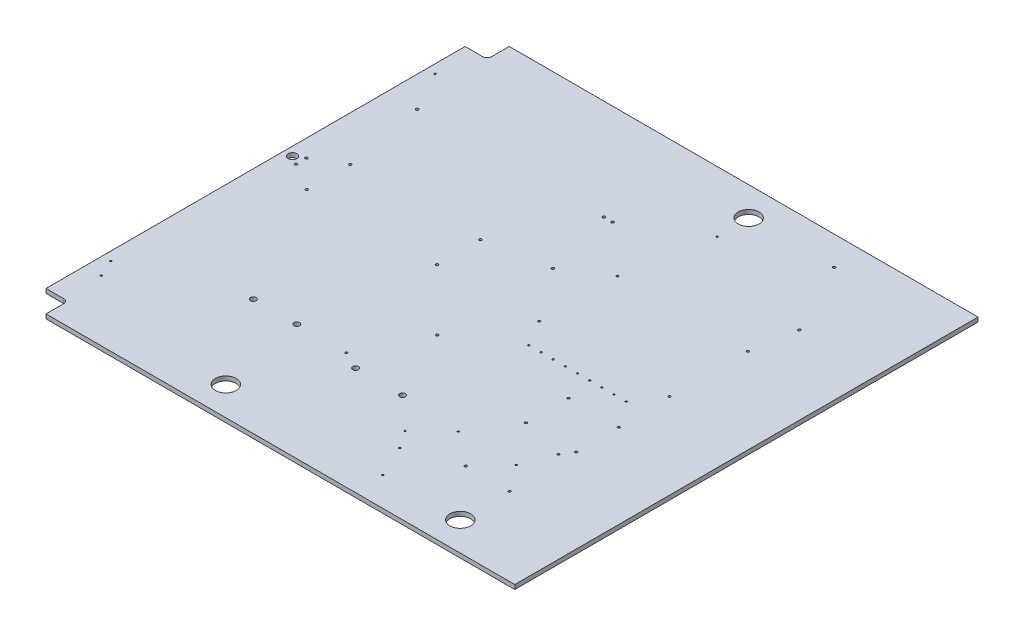
SolidWorks part; units mm, degrees
ref_plane "Front Plane" through (0, 0, 0) normal (0, 0, 1) x (1, 0, 0)
ref_plane "Top Plane" through (0, 0, 0) normal (0, 1, 0) x (1, 0, 0)
ref_plane "Right Plane" through (0, 0, 0) normal (1, 0, 0) x (0, 0, -1)
sketch "Sketch1" plane through (0, 0, 0) normal (1, 0, 0) x (0, 0, -1)
  line L0 (0, 0) -> (-533.4, 0)
  line L1 (-533.4, 0) -> (-533.4, 5)
  line L2 (-533.4, 5) -> (0, 5)
  line L6 (0, 5) -> (0, 0)
  dimension "D1" = 533.4
extrude "Boss-Extrude1" add sketch "Sketch1" along normal blind 565.15
sketch "BotthomHoles-Sketch2" plane through (0, 5, 0) normal (0, 1, 0) x (1, 0, 0)
  line L1 (565.15, 0) -> (565.15, -533.4) construction
  line L2 (565.15, -533.4) -> (0, -533.4) construction
  line L3 (565.15, 0) -> (0, 0) construction
  line L4 (0, 0) -> (0, -533.4) construction
  circle A0 centre (334.275, -33.175) radius 12
  circle A25 centre (199.275, -500.225) radius 12
  circle A26 centre (469.275, -500.225) radius 12
  dimension "D10" = 24
  dimension "D2" = 95.875
  dimension "D3" = 270
  dimension "D4" = 135
  dimension "D5" = 33.175
  dimension "D6" = 33.175
  dimension "D8" = 500.225
  dimension "D7" = 199.275
  dimension "D9" = 334.275
  dimension "D11" = 469.275
extrude "BottomStepperHoles-Cut-Extrude1" cut sketch "BotthomHoles-Sketch2" against normal through all
sketch "BottomPSUHolesSketch2" plane through (0, 5, 0) normal (0, 1, 0) x (1, 0, 0)
  line L0 (0, 0) -> (0, -533.4) construction
  line L1 (565.15, -533.4) -> (0, -533.4) construction
  line L2 (565.15, 0) -> (0, 0) construction
  circle A0 centre (201.5, -209.2) radius 1.5
  circle A1 centre (201.5, -259.2) radius 1.5
  circle A2 centre (51.5, -209.2) radius 1.5
  circle A3 centre (51.5, -259.2) radius 1.5
  circle A6 centre (180, -399.2) radius 3.25
  circle A7 centre (130, -399.2) radius 3.25
  circle A8 centre (257.75, -409.2) radius 3.25
  circle A9 centre (311.75, -409.2) radius 3.25
  dimension "D4" = 6.5
  dimension "D3" = 51.5
  dimension "D1" = 150
  dimension "D2" = 50
  dimension "D7" = 209.2
  dimension "D5" = 50
  dimension "D8" = 140
  dimension "D10" = 134.2
  dimension "D11" = 274.2
  dimension "D12" = 324.2
  dimension "D13" = 201.5
  dimension "D14" = 54
  dimension "D15" = 77.75
  dimension "D16" = 10
  dimension "D9" = 78.5
  dimension "D17" = 130
  dimension "D18" = 124.2
  dimension "D19" = 257.75
  dimension "D20" = 311.75
extrude "BottomPSUHolesCut-Extrude1" cut sketch "BottomPSUHolesSketch2" against normal through all
sketch "OctopusHolesSketch2" plane through (0, 5, 0) normal (0, 1, 0) x (1, 0, 0)
  line L0 (0, 0) -> (0, -533.4) construction
  line L1 (565.15, -533.4) -> (0, -533.4) construction
  circle A0 centre (316.75, -256.7) radius 1.35
  circle A1 centre (466.75, -256.7) radius 1.35
  circle A2 centre (316.75, -166.7) radius 1.35
  circle A3 centre (466.75, -166.7) radius 1.35
  dimension "D1" = 150
  dimension "D3" = 2.7
  dimension "D2" = 90
  dimension "D4" = 115.25
  dimension "D5" = 42.5
  dimension "D6" = 316.75
  dimension "D7" = 466.75
  dimension "D8" = 276.7
  dimension "D9" = 366.7
extrude "OctopusMountHolesCut-Extrude1" cut sketch "OctopusHolesSketch2" against normal through all
sketch "PowrCableGuideMountHolesSketch2" plane through (0, 5, 0) normal (0, 1, 0) x (1, 0, 0)
  line L0 (0, 0) -> (0, -533.4) construction
  line L1 (565.15, -533.4) -> (0, -533.4) construction
  circle A0 centre (271.75, -329.2) radius 1.5
  circle A1 centre (271.75, -196.2) radius 1.5
  dimension "D2" = 3
  dimension "D1" = 133
  dimension "D3" = 45
  dimension "D5" = 271.75
  dimension "D6" = 337.2
  dimension "D7" = 204.2
  dimension "D4" = 29.5
extrude "PowerCableGuideMountHolesCut-Extrude1" cut sketch "PowrCableGuideMountHolesSketch2" against normal through all
sketch "RPIHolesSketch2" plane through (0, 5, 0) normal (0, 1, 0) x (1, 0, 0)
  line L0 (0, 0) -> (0, -533.4) construction
  line L1 (565.15, -533.4) -> (0, -533.4) construction
  circle A4 centre (468.25, -316.7) radius 1.35
  circle A5 centre (468.25, -365.7) radius 1.35
  circle A6 centre (410.25, -316.7) radius 1.35
  circle A7 centre (410.25, -365.7) radius 1.35
  point P4 (282.575, -533.4)
  dimension "D7" = 2.7
  dimension "D1" = 58
  dimension "D2" = 49
  dimension "D3" = 60
  dimension "D4" = 1.5
  dimension "D5" = 410.25
  dimension "D6" = 468.25
  dimension "D8" = 167.7
  dimension "D9" = 216.7
extrude "RPIMountHolesCut-Extrude1" cut sketch "RPIHolesSketch2" against normal through all
sketch "DragChainAndCableGuideHolesSketch2" plane through (0, 5, 0) normal (0, 1, 0) x (1, 0, 0)
  line L3 (565.15, -533.4) -> (0, -533.4) construction
  line L9 (0, 0) -> (0, -533.4) construction
  circle A11 centre (260, -115.65) radius 1.5
  circle A12 centre (10, -234.2) radius 5
  circle A17 centre (475, -115.65) radius 1.5
  circle A18 centre (250, -115.65) radius 1.5
  circle A19 centre (35, -115.65) radius 1.5
  circle A20 centre (20, -240.2) radius 1.5
  circle A21 centre (20, -228.2) radius 1.5
  dimension "D17" = 3
  dimension "D10" = 10
  dimension "D26" = 3
  dimension "D13" = 299.2
  dimension "D15" = 260
  dimension "D5" = 215
  dimension "D16" = 8.25
  dimension "D18" = 475
  dimension "D19" = 215
  dimension "D20" = 10
  dimension "D22" = 35
  dimension "D23" = 250
  dimension "D6" = 25
  dimension "D11" = 10
  dimension "D21" = 6
  dimension "D24" = 6
  dimension "D25" = 20
  dimension "D3" = 417.75
extrude "CragChainAndCableGuideHolesCut-Extrude1" cut sketch "DragChainAndCableGuideHolesSketch2" against normal through all
sketch "Sketch2" plane through (0, 5, 0) normal (0, 1, 0) x (1, 0, 0)
  line L0 (565.15, -533.4) -> (0, -533.4) construction
  line L1 (0, 0) -> (0, -533.4) construction
  circle A0 centre (334.75, -286.7) radius 1
  circle A1 centre (348.75, -286.7) radius 1
  circle A2 centre (362.75, -286.7) radius 1
  circle A3 centre (376.75, -286.7) radius 1
  circle A4 centre (390.75, -286.7) radius 1
  circle A5 centre (404.75, -286.7) radius 1
  circle A6 centre (418.75, -286.7) radius 1
  circle A7 centre (432.75, -286.7) radius 1
  circle A8 centre (446.75, -286.7) radius 1
  dimension "D10" = 14
  dimension "D11" = 2
  dimension "D1" = 18
  dimension "D2" = 14
  dimension "D3" = 14
  dimension "D4" = 14
  dimension "D5" = 14
  dimension "D6" = 14
  dimension "D7" = 14
  dimension "D8" = 14
  dimension "D9" = 30
  dimension "D12" = 246.7
  dimension "D13" = 334.75
extrude "OctopusRouting holesCut-Extrude1" cut sketch "Sketch2" against normal through all
sketch "PiPowerAndSSRControlSketch3" plane through (0, 5, 0) normal (0, 1, 0) x (1, 0, 0)
  line L0 (565.15, -533.4) -> (0, -533.4) construction
  line L1 (0, 0) -> (0, -533.4) construction
  line L2 (565.15, -533.4) -> (0, -533.4) construction
  circle A10 centre (237, -399.2) radius 1.25
  circle A11 centre (460.5, -378.4) radius 1.25
  dimension "D16" = 134.2
  dimension "D18" = 237
  dimension "D19" = 460.5
  dimension "D20" = 155
extrude "PiPowerAndSSRControlCuts-Extrude1" cut sketch "PiPowerAndSSRControlSketch3" against normal through all
sketch "CornerCableKnotchesSketch4" plane through (0, 5, 0) normal (0, 1, 0) x (1, 0, 0)
  line L0 (0, -25.4) -> (20.4, -25.4)
  line L1 (25.4, 0) -> (25.4, -20.4)
  line L2 (565.15, 0) -> (0, 0) construction
  line L3 (0, -25.4) -> (0, 0)
  line L4 (0, 0) -> (0, -533.4) construction
  line L5 (0, 0) -> (25.4, 0)
  line L6 (0, -508) -> (20.4, -508)
  line L7 (25.4, -513) -> (25.4, -533.4)
  line L8 (565.15, -533.4) -> (0, -533.4) construction
  line L9 (0, -508) -> (0, -533.4)
  line L10 (0, -533.4) -> (25.4, -533.4)
  arc A0 (20.4, -25.4) -> (25.4, -20.4) centre (20.4, -20.4) ccw
  arc A1 (25.4, -513) -> (20.4, -508) centre (20.4, -513) ccw
  circle A2 centre (25, -115.65) radius 5 construction
  dimension "D1" = 25.4
extrude "CornerCableKnotchCut-Extrude1" cut sketch "CornerCableKnotchesSketch4" against normal through all
sketch "Z1 pathsSketch4" plane through (0, 5, 0) normal (0, 1, 0) x (1, 0, 0)
  line L2 (0, -25.4) -> (0, -508) construction
  line L3 (565.15, -533.4) -> (25.4, -533.4) construction
  circle A0 centre (432.75, -33.175) radius 1.5
  circle A1 centre (475, -115.65) radius 1.5 construction
  dimension "D1" = 432.75
  dimension "D2" = 500.225
extrude "Z1 patgsCut-Extrude1" cut sketch "Z1 pathsSketch4" against normal through all
sketch "Z2PathsSketch5" plane through (0, 5, 0) normal (0, 1, 0) x (1, 0, 0)
  line L0 (565.15, -533.4) -> (25.4, -533.4) construction
  line L1 (0, -25.4) -> (0, -508) construction
  circle A0 centre (380, -500.225) radius 1
  circle A1 centre (380, -413.4) radius 1
  circle A2 centre (446.75, -413.4) radius 1
  circle A3 centre (446.75, -286.7) radius 1 construction
  dimension "D1" = 33.175
  dimension "D2" = 120
  dimension "D3" = 380
  dimension "D4" = 446.75
extrude "Z2PathsCut-Extrude2" cut sketch "Z2PathsSketch5" against normal through all
sketch "ZPathsSketch4" plane through (0, 5, 0) normal (0, 1, 0) x (1, 0, 0)
  line L0 (565.15, -533.4) -> (25.4, -533.4) construction
  line L1 (0, -25.4) -> (0, -508) construction
  circle A0 centre (469.275, -443.4) radius 1.35
  circle A1 centre (418.75, -443.4) radius 1.35
  circle A2 centre (410.25, -365.7) radius 1.35 construction
  dimension "D1" = 90
  dimension "D2" = 469.275
  dimension "D3" = 418.75
extrude "ZPathsCut-Extrude1" cut sketch "ZPathsSketch4" against normal through all
sketch "LeftGantryAndExtruderPathsSketch4" plane through (0, 5, 0) normal (0, 1, 0) x (1, 0, 0)
  line L0 (565.15, -533.4) -> (25.4, -533.4) construction
  line L1 (0, -25.4) -> (0, -508) construction
  circle A0 centre (348.75, -443.4) radius 1
  circle A1 centre (362.75, -463.4) radius 1
  circle A2 centre (334.75, -286.7) radius 1 construction
  circle A3 centre (10, -443.4) radius 1
  circle A4 centre (19, -463.4) radius 1
  dimension "D1" = 70
  dimension "D2" = 90
  dimension "D3" = 10
  dimension "D4" = 19
  dimension "D5" = 348.75
  dimension "D6" = 362.75
extrude "LeftGantryAndExtruderPathsCut-Extrude1" cut sketch "LeftGantryAndExtruderPathsSketch4" against normal through all
sketch "RightGantryPathsSketch5" plane through (0, 5, 0) normal (0, 1, 0) x (1, 0, 0)
  line L0 (565.15, -533.4) -> (25.4, -533.4) construction
  line L1 (0, -25.4) -> (0, -508) construction
  circle A0 centre (334.75, -70) radius 1
  circle A1 centre (334.75, -286.7) radius 1 construction
  circle A2 centre (10, -70) radius 1
  dimension "D1" = 463.4
  dimension "D2" = 10
  dimension "D3" = 334.75
extrude "RightGantryPathsCut-Extrude2" cut sketch "RightGantryPathsSketch5" against normal through all
equation "\"RailThickness\"= .125in'Spec"
equation "\"Nema17MountStepperHoleDiameter\"= 24mm'Spec"
equation "\"SideRailLength\"= 21.75in"
equation "\"D10@BotthomHoles-Sketch2\" = \"Nema17MountStepperHoleDiameter\""
equation "\"D1@Boss-Extrude1\"=\"LowerEnclosureLength\""
equation "\"BedLength\"= \"BuildPlateLength\""
equation "\"DistanceBetweenFrontToBackStepperHoles\"= \"BedLength\" - \"BuildPlateStandoffHolesDistanceFromFrontOrBackSide\" * 2'Equals 270"
equation "\"LowerEnclosureThickness\"= 5mm"
equation "\"FrontOrBackRailLength\"= 20.5in"
equation "\"D1@Sketch1\"=\"LowerEncloseWidth\""
equation "\"D2@Sketch1\"=\"LowerEnclosureThickness\""
equation "\"24VPSUMountingHolesShortDistanceBetween\"= 50mm'Yours may differ"
equation "\"24VPSUMountingHolesLongDistanceBetween\"= 150mm'Yours may differ"
equation "\"24VPSUMountingHoleOffsetFromEitherSide\"= 32.5mm'Yours may differ"
equation "\"24VPSUMountingHoleDiameter\"= 3mm'Yours may differ"
equation "\"D6@BottomPSUHolesSketch2\" = \"24VPSUMountingHoleDiameter\""
equation "\"RPi4BoardMountingHoleDiameter\"= 2.7mm'Spec"
equation "\"OctopusV1.1BoardMountingHoleOffsetFromAllEdges\"= 5mm'Spec"
equation "\"OctopusV1.1BoardMountingHoleLengthDistanceBetween\"= 150mm'Spec"
equation "\"OctopusV1.1BoardMountingHoleWidthDistanceBetween\"= 90mm'Spec"
equation "\"D7@RPIHolesSketch2\" = \"RPi4BoardMountingHoleDiameter\""
equation "\"RPi4BoardMountingHoleLengthDistanceBetween\"= 58mm'Spec"
equation "\"OctopusV1.1BoardMountingHoleDiameter\"= 2.7mm'Spec"
equation "\"CWD4890MountingHoleWidthDistance\"= 50mm'Spec"
equation "\"24VPSULength\"= 213mm'Spec"
equation "\"D3@OctopusHolesSketch2\"=\"OctopusV1.1BoardMountingHoleDiameter\""
equation "\"24VPSUMountingHoleOffsetFromFront\"= 32.5mm"
equation "\"DistanceBetween24VPSUAndOctopus\"= \"24VPSUMountingHoleOffsetFromFront\" + \"OctopusV1.1BoardMountingHoleOffsetFromAllEdges\" + 77.75'77.75mm gives 10mm before and after 60mm cable guide"
equation "\"GapBetweenVerticalSupportsAndRails\"= \"RailThickness\" * 2"
equation "\"LowerEncloseWidth\"= \"FrontOrBackRailLength\" + \"GapBetweenVerticalSupportsAndRails\" * 2"
equation "\"Nema17MountStepperHoleFromBack\"= 30mm"
equation "\"D2@BotthomHoles-Sketch2\"=\"DistanceFromFrontSideToFirstLeftStepperHoleMountYSValue\" + \"Nema17StepperMountSlotDistance\"/2 + \"GapBetweenVerticalSupportsAndRails\""
equation "\"D3@BotthomHoles-Sketch2\"=\"DistanceBetweenFrontToBackStepperHoles\""
equation "\"D4@BotthomHoles-Sketch2\"=\"DistanceBetweenFrontToBackStepperHoles\"/2"
equation "\"D5@BotthomHoles-Sketch2\"=\"Nema17MountStepperHoleFromBack\" + \"RailThickness\""
equation "\"D6@BotthomHoles-Sketch2\"=\"Nema17MountStepperHoleFromBack\" + \"RailThickness\""
equation "\"LowerEnclosureLength\"= \"SideRailLength\" + \"GapBetweenVerticalSupportsAndRails\" * 2"
equation "\"DistanceFromFrontSideToFirstLeftStepperHoleMountYSValue\"= 74.025mm"
equation "\"BuildPlateStandoffHolesDistanceFromFrontOrBackSide\"= 41mm"
equation "\"BuildPlateLength\"= 352mm'Spec"
equation "\"D1@BottomPSUHolesSketch2\"=\"24VPSUMountingHolesLongDistanceBetween\""
equation "\"D2@BottomPSUHolesSketch2\"=\"24VPSUMountingHolesShortDistanceBetween\""
equation "\"24VPSUOffsetFromBack\"= ( \"24VPSULength\" - \"24VPSUMountingHolesLongDistanceBetween\" ) / 2 + 20mm"
equation "\"24VPSUOffsetFromRightSide\"= ( \"LowerEncloseWidth\" - \"24VPSUWidth\" ) / 2"
equation "\"24VPSUWidth\"= 115mm'Yours may differ"
equation "\"D3@BottomPSUHolesSketch2\"=\"24VPSUOffsetFromBack\""
equation "\"D1@OctopusHolesSketch2\"=\"OctopusV1.1BoardMountingHoleLengthDistanceBetween\""
equation "\"D2@OctopusHolesSketch2\"=\"OctopusV1.1BoardMountingHoleWidthDistanceBetween\""
equation "\"D4@OctopusHolesSketch2\" = \"DistanceBetween24VPSUAndOctopus\""
equation "\"RPI4BoardMountingHoleWidthDistanceBetween\"= 49mm"
equation "\"D7@BottomPSUHolesSketch2\"=\"24VPSUOffsetFromRightSide\""
equation "\"D1@RPIHolesSketch2\"=\"RPi4BoardMountingHoleLengthDistanceBetween\""
equation "\"D2@RPIHolesSketch2\"=\"RPI4BoardMountingHoleWidthDistanceBetween\""
equation "\"D5@BottomPSUHolesSketch2\"=\"CWD4890MountingHoleWidthDistance\""
equation "\"OctopusV1.1ToPSUNegTerminalOffset\"= \"24VPSUNegTerminalOffsetFromSide\" - \"24VPSUMountingHoleOffsetFromEitherSide\" + \"OctopusV1.1NegTerminalOffsetFromSide\" + \"OctopusV1.1BoardMountingHoleOffsetFromAllEdges\""
equation "\"24VPSUNegTerminalOffsetFromSide\"= 50.5mm"
equation "\"OctopusV1.1NegTerminalOffsetFromSide\"= 19.5mm"
equation "\"D5@OctopusHolesSketch2\" = \"OctopusV1.1ToPSUNegTerminalOffset\""
equation "\"PowerCableGuideMountingHoleDistanceBetweenValue\"=133"
equation "\"D1@PowrCableGuideMountHolesSketch2\" = \"PowerCableGuideMountingHoleDistanceBetweenValue\""
equation "\"D2@PowrCableGuideMountHolesSketch2\" = \"24VPSUMountingHoleDiameter\""
equation "\"RCNUNMountingHoleWidthDistance\"= 54mm"
equation "\"D14@BottomPSUHolesSketch2\"=\"RCNUNMountingHoleWidthDistance\""
equation "\"OctopusToPowerCableGuideOffset\"= 29.5mm'This asligned perfectly"
equation "\"D4@PowrCableGuideMountHolesSketch2\"=\"OctopusToPowerCableGuideOffset\""
equation "\"VSWidth\"= 1.25in'Spec"
equation "\"D1@CornerCableKnotchesSketch4\" = \"VSWidth\" - \"RailThickness\" * 2"
equation "\"Nema17StepperMountSlotDistance\"= 31mm'Spec"
equation "\"D6@DragChainAndCableGuideHolesSketch2\" = \"24VPSUMountingHolesShortDistanceBetween\" / 2"
